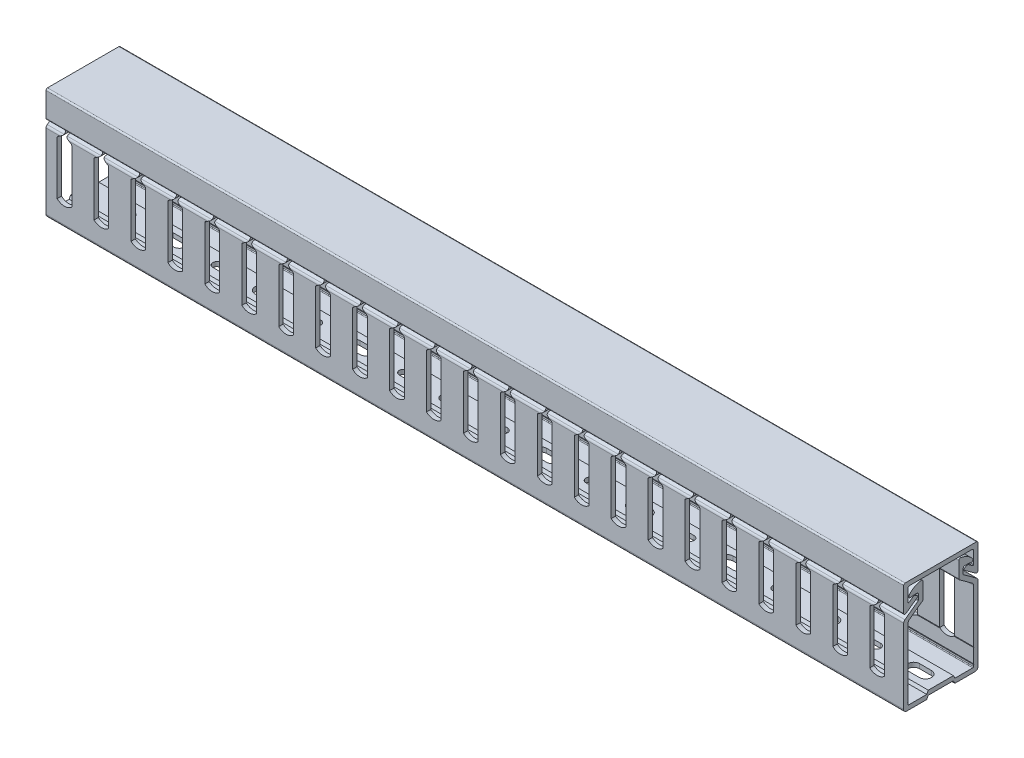
SolidWorks part; units mm, degrees
ref_plane "Alzado" through (0, 0, 0) normal (0, 0, 1) x (1, 0, 0)
ref_plane "Planta" through (0, 0, 0) normal (0, 1, 0) x (1, 0, 0)
ref_plane "Vista lateral" through (0, 0, 0) normal (1, 0, 0) x (0, 0, -1)
sketch "Croquis1" plane through (0, 0, 0) normal (1, 0, 0) x (0, 0, -1)
  line L0 (19.2861, 41.3685) -> (12.1583, 46.5609)
  line L1 (16.9056, 40.2266) -> (9.9464, 45.2924)
  line L2 (17.1611, 50.9204) -> (17.1611, 50.9657)
  line L3 (-7.5409, 0.7912) -> (-6.7469, 2.38)
  line L4 (-6.7469, 2.38) -> (-3.175, 2.38)
  line L5 (-7.5413, -1.5888) -> (-6.7469, 0)
  line L6 (-6.7469, 0) -> (-3.175, 0)
  line L7 (-7.5413, -1.5888) -> (-18.3513, -1.5888)
  line L8 (-3.175, 2.38) -> (3.175, 2.38)
  line L9 (-3.175, 0) -> (3.175, 0)
  line L10 (-17.5588, 10.0456) -> (-17.5588, 2.4512)
  line L11 (-17.162, 0.7912) -> (-7.5409, 0.7912)
  line L12 (-17.856, 2.2796) -> (-17.5588, 2.4512)
  line L13 (-17.856, 2.2796) -> (-17.5588, 2.1081)
  line L14 (-17.5588, 2.1081) -> (-17.5588, 1.1881)
  line L15 (-17.856, 10.2171) -> (-17.5588, 10.0456)
  line L16 (-17.856, 10.2171) -> (-17.5588, 10.3887)
  line L17 (17.5588, 10.0456) -> (17.5588, 2.4512)
  line L18 (17.5588, 2.1081) -> (17.5588, 1.1881)
  line L19 (17.856, 2.2796) -> (17.5588, 2.1081)
  line L20 (17.856, 2.2796) -> (17.5588, 2.4512)
  line L21 (17.856, 10.2171) -> (17.5588, 10.3887)
  line L22 (17.856, 10.2171) -> (17.5588, 10.0456)
  line L23 (17.5588, 38.9431) -> (17.5588, 10.3887)
  line L24 (19.9388, -0.0013) -> (19.9388, 40.0854)
  line L25 (12.0017, 46.8688) -> (12.0017, 49.624)
  line L26 (9.6198, 45.9342) -> (9.6198, 54.439)
  line L27 (14.842, 50.4074) -> (16.2738, 50.1687)
  line L28 (12.7954, 50.4177) -> (14.7167, 50.4177)
  line L29 (-19.2861, 41.3685) -> (-12.1583, 46.5609)
  line L30 (-16.9056, 40.2266) -> (-9.9464, 45.2924)
  line L31 (-9.6198, 45.9342) -> (-9.6198, 54.439)
  line L32 (-12.7954, 50.4177) -> (-14.7167, 50.4177)
  line L33 (-12.0017, 46.8688) -> (-12.0017, 49.624)
  line L34 (-14.842, 50.4074) -> (-16.2738, 50.1687)
  line L35 (-17.1611, 50.9204) -> (-17.1611, 50.9657)
  line L36 (-17.5588, 38.9431) -> (-17.5588, 10.3887)
  line L37 (-19.9388, -0.0013) -> (-19.9388, 40.0854)
  line L38 (3.175, 0) -> (6.7469, 0)
  line L39 (6.7469, 0) -> (7.5413, -1.5888)
  line L40 (7.5413, -1.5888) -> (18.3513, -1.5888)
  line L41 (17.162, 0.7912) -> (7.5413, 0.7912)
  line L42 (7.5413, 0.7912) -> (6.7469, 2.38)
  line L43 (6.7469, 2.38) -> (3.175, 2.38)
  arc A0 (-17.5588, 1.1881) -> (-17.162, 0.7912) centre (-17.162, 1.1881) ccw
  arc A1 (-19.9388, -0.0013) -> (-18.3513, -1.5888) centre (-18.3513, -0.0013) ccw
  arc A2 (17.162, 0.7912) -> (17.5588, 1.1881) centre (17.162, 1.1881) ccw
  arc A3 (18.3513, -1.5888) -> (19.9388, -0.0013) centre (18.3513, -0.0013) ccw
  arc A4 (19.9388, 40.0854) -> (19.2861, 41.3685) centre (18.3513, 40.0854) ccw
  arc A5 (17.5588, 38.9431) -> (16.9056, 40.2266) centre (15.9713, 38.9431) ccw
  arc A6 (12.0017, 46.8688) -> (12.1583, 46.5609) centre (12.3827, 46.8688) ccw
  arc A7 (9.6198, 45.9342) -> (9.9464, 45.2924) centre (10.4136, 45.9342) ccw
  arc A8 (12.7954, 50.4177) -> (12.0017, 49.624) centre (12.7954, 49.624) ccw
  arc A9 (10.688, 55.1838) -> (9.6198, 54.439) centre (10.4136, 54.439) ccw
  arc A10 (16.86, 51.7867) -> (10.688, 55.1838) centre (9.3251, 45.4023) ccw
  arc A11 (17.1611, 50.9657) -> (16.86, 51.7867) centre (15.8911, 50.9657) ccw
  arc A12 (16.2738, 50.1687) -> (17.1611, 50.9204) centre (16.3991, 50.9204) ccw
  arc A13 (14.842, 50.4074) -> (14.7167, 50.4177) centre (14.7167, 49.6557) ccw
  arc A14 (-9.9464, 45.2924) -> (-9.6198, 45.9342) centre (-10.4136, 45.9342) ccw
  arc A15 (-16.9056, 40.2266) -> (-17.5588, 38.9431) centre (-15.9713, 38.9431) ccw
  arc A16 (-19.2861, 41.3685) -> (-19.9388, 40.0854) centre (-18.3513, 40.0854) ccw
  arc A17 (-9.6198, 54.439) -> (-10.688, 55.1838) centre (-10.4136, 54.439) ccw
  arc A18 (-16.86, 51.7867) -> (-17.1611, 50.9657) centre (-15.8911, 50.9657) ccw
  arc A19 (-12.1583, 46.5609) -> (-12.0017, 46.8688) centre (-12.3827, 46.8688) ccw
  arc A20 (-12.0017, 49.624) -> (-12.7954, 50.4177) centre (-12.7954, 49.624) ccw
  arc A21 (-14.7167, 50.4177) -> (-14.842, 50.4074) centre (-14.7167, 49.6557) ccw
  arc A22 (-17.1611, 50.9204) -> (-16.2738, 50.1687) centre (-16.3991, 50.9204) ccw
  arc A23 (-10.688, 55.1838) -> (-16.86, 51.7867) centre (-9.3251, 45.4023) ccw
  point P92 (0, 0)
extrude "Saliente-Extruir1" add sketch "Croquis1" along normal mid plane 762
sketch "Croquis5" plane through (0, 2.38, 0) normal (0, 1, 0) x (1, 0, 0)
  line L157 (-379.0156, -3.2514) -> (-381, -3.2514)
  line L158 (-379.0156, 3.251) -> (-381, 3.251)
  line L159 (-335.6864, 3.251) -> (-329.3364, 3.251)
  line L160 (-335.6864, -3.2514) -> (-329.3364, -3.2514)
  line L161 (-235.6612, -3.2514) -> (-229.3112, -3.2514)
  line L162 (-235.6612, 3.251) -> (-229.3112, 3.251)
  line L163 (-285.6738, -3.2514) -> (-279.3238, -3.2514)
  line L164 (-285.6738, 3.251) -> (-279.3238, 3.251)
  line L165 (-185.6486, -3.2514) -> (-179.2986, -3.2514)
  line L166 (-185.6486, 3.251) -> (-182.1992, 3.251)
  line L167 (-309.2402, 2.2477) -> (-305.7446, 2.2477)
  line L168 (-309.2402, -2.2481) -> (-305.7446, -2.2481)
  line L169 (-355.7826, -2.2481) -> (-359.2782, -2.2481)
  line L170 (-355.7826, 2.2477) -> (-359.2782, 2.2477)
  line L171 (-259.2276, -2.2481) -> (-255.732, -2.2481)
  line L172 (-259.2276, 2.2477) -> (-255.732, 2.2477)
  line L173 (-209.215, -2.2481) -> (-205.7194, -2.2481)
  line L174 (-209.215, 2.2477) -> (-205.7194, 2.2477)
  line L188 (-398.7832, -0.0002) -> (-161.8215, -0.0002) construction
  arc A105 (-379.0156, -3.2514) -> (-379.0156, 3.251) centre (-379.0156, -0.0002) ccw
  arc A106 (-329.3364, -3.2514) -> (-329.3364, 3.251) centre (-329.3364, -0.0002) ccw
  arc A107 (-335.6864, 3.251) -> (-335.6864, -3.2514) centre (-335.6864, -0.0002) ccw
  circle A108 centre (-332.5114, -0.0002) radius 6.677
  circle A109 centre (-332.5114, -0.0002) radius 7.4708
  circle A110 centre (-232.4862, -0.0002) radius 6.677
  circle A111 centre (-232.4862, -0.0002) radius 7.4708
  arc A112 (-229.3112, -3.2514) -> (-229.3112, 3.251) centre (-229.3112, -0.0002) ccw
  arc A113 (-235.6612, 3.251) -> (-235.6612, -3.2514) centre (-235.6612, -0.0002) ccw
  arc A114 (-279.3238, -3.2514) -> (-279.3238, 3.251) centre (-279.3238, -0.0002) ccw
  arc A115 (-285.6738, 3.251) -> (-285.6738, -3.2514) centre (-285.6738, -0.0002) ccw
  arc A116 (-179.2986, -3.2514) -> (-178.0729, -3.0115) centre (-179.2986, -0.0002) ccw
  arc A117 (-185.6486, 3.251) -> (-185.6486, -3.2514) centre (-185.6486, -0.0002) ccw
  arc A118 (-309.2402, 2.2477) -> (-309.2402, -2.2481) centre (-309.2402, -0.0002) ccw
  arc A119 (-305.7446, -2.2481) -> (-305.7446, 2.2477) centre (-305.7446, -0.0002) ccw
  arc A120 (-359.2782, 2.2477) -> (-359.2782, -2.2481) centre (-359.2782, -0.0002) ccw
  arc A121 (-355.7826, -2.2481) -> (-355.7826, 2.2477) centre (-355.7826, -0.0002) ccw
  arc A122 (-255.732, -2.2481) -> (-255.732, 2.2477) centre (-255.732, -0.0002) ccw
  arc A123 (-259.2276, 2.2477) -> (-259.2276, -2.2481) centre (-259.2276, -0.0002) ccw
  arc A124 (-205.7194, -2.2481) -> (-205.7194, 2.2477) centre (-205.7194, -0.0002) ccw
  arc A125 (-209.215, 2.2477) -> (-209.215, -2.2481) centre (-209.215, -0.0002) ccw
  point P817 (-381, 3.251)
  point P818 (-381, -3.2514)
  point P820 (-359.2782, 2.2477)
  point P821 (-359.2782, -2.2481)
  point P823 (-361.5261, -0.0002)
  point P824 (-353.5347, -0.0002)
  point P826 (-285.6738, 3.251)
  point P827 (-285.6738, -3.2514)
  point P829 (-288.925, -0.0002)
  point P830 (-276.0726, -0.0002)
sketch "Croquis6" plane through (0, 2.38, 0) normal (0, 1, 0) x (1, 0, 0)
  line L5 (0, 0) -> (-149.8099, 0) construction
  line L6 (-382.9844, 0) -> (-379.0156, 0) construction
  line L7 (-382.9844, 3.25) -> (-379.0156, 3.25)
  line L8 (-382.9844, -3.25) -> (-379.0156, -3.25)
  line L10 (-381, 6.7469) -> (-381, -6.7469) construction
  line L11 (-355.7826, 0) -> (-359.2782, 0) construction
  line L12 (-355.7826, -2.25) -> (-359.2782, -2.25)
  line L13 (-355.7826, 2.25) -> (-359.2782, 2.25)
  line L14 (-305.7446, 0) -> (-309.2402, 0) construction
  line L15 (-305.7446, -2.25) -> (-309.2402, -2.25)
  line L16 (-305.7446, 2.25) -> (-309.2402, 2.25)
  line L17 (-255.7066, 0) -> (-259.2022, 0) construction
  line L18 (-255.7066, -2.25) -> (-259.2022, -2.25)
  line L19 (-255.7066, 2.25) -> (-259.2022, 2.25)
  line L20 (-205.6686, 0) -> (-209.1642, 0) construction
  line L21 (-205.6686, -2.25) -> (-209.1642, -2.25)
  line L22 (-205.6686, 2.25) -> (-209.1642, 2.25)
  line L23 (-155.6306, 0) -> (-159.1262, 0) construction
  line L24 (-155.6306, -2.25) -> (-159.1262, -2.25)
  line L25 (-155.6306, 2.25) -> (-159.1262, 2.25)
  line L26 (-105.5926, 0) -> (-109.0882, 0) construction
  line L27 (-105.5926, -2.25) -> (-109.0882, -2.25)
  line L28 (-105.5926, 2.25) -> (-109.0882, 2.25)
  line L29 (-55.5546, 0) -> (-59.0502, 0) construction
  line L30 (-55.5546, -2.25) -> (-59.0502, -2.25)
  line L31 (-55.5546, 2.25) -> (-59.0502, 2.25)
  line L32 (-5.5166, 0) -> (-9.0122, 0) construction
  line L33 (-5.5166, -2.25) -> (-9.0122, -2.25)
  line L34 (-5.5166, 2.25) -> (-9.0122, 2.25)
  line L35 (44.5214, 0) -> (41.0258, 0) construction
  line L36 (44.5214, -2.25) -> (41.0258, -2.25)
  line L37 (44.5214, 2.25) -> (41.0258, 2.25)
  line L38 (94.5594, 0) -> (91.0638, 0) construction
  line L39 (94.5594, -2.25) -> (91.0638, -2.25)
  line L40 (94.5594, 2.25) -> (91.0638, 2.25)
  line L41 (144.5974, 0) -> (141.1018, 0) construction
  line L42 (144.5974, -2.25) -> (141.1018, -2.25)
  line L43 (144.5974, 2.25) -> (141.1018, 2.25)
  line L44 (194.6354, 0) -> (191.1398, 0) construction
  line L45 (194.6354, -2.25) -> (191.1398, -2.25)
  line L46 (194.6354, 2.25) -> (191.1398, 2.25)
  line L47 (244.6734, 0) -> (241.1778, 0) construction
  line L48 (244.6734, -2.25) -> (241.1778, -2.25)
  line L49 (244.6734, 2.25) -> (241.1778, 2.25)
  line L50 (294.7114, 0) -> (291.2158, 0) construction
  line L51 (294.7114, -2.25) -> (291.2158, -2.25)
  line L52 (294.7114, 2.25) -> (291.2158, 2.25)
  line L53 (344.7494, 0) -> (341.2538, 0) construction
  line L54 (344.7494, -2.25) -> (341.2538, -2.25)
  line L55 (344.7494, 2.25) -> (341.2538, 2.25)
  line L56 (394.7874, 0) -> (391.2918, 0) construction
  line L57 (394.7874, -2.25) -> (391.2918, -2.25)
  line L58 (394.7874, 2.25) -> (391.2918, 2.25)
  arc A3 (-382.9844, 3.25) -> (-382.9844, -3.25) centre (-382.9844, 0) ccw
  arc A4 (-379.0156, -3.25) -> (-379.0156, 3.25) centre (-379.0156, 0) ccw
  arc A5 (-355.7826, -2.25) -> (-355.7826, 2.25) centre (-355.7826, 0) ccw
  arc A6 (-359.2782, 2.25) -> (-359.2782, -2.25) centre (-359.2782, 0) ccw
  arc A7 (-305.7446, -2.25) -> (-305.7446, 2.25) centre (-305.7446, 0) ccw
  arc A8 (-309.2402, 2.25) -> (-309.2402, -2.25) centre (-309.2402, 0) ccw
  arc A9 (-255.7066, -2.25) -> (-255.7066, 2.25) centre (-255.7066, 0) ccw
  arc A10 (-259.2022, 2.25) -> (-259.2022, -2.25) centre (-259.2022, 0) ccw
  arc A11 (-205.6686, -2.25) -> (-205.6686, 2.25) centre (-205.6686, 0) ccw
  arc A12 (-209.1642, 2.25) -> (-209.1642, -2.25) centre (-209.1642, 0) ccw
  arc A13 (-155.6306, -2.25) -> (-155.6306, 2.25) centre (-155.6306, 0) ccw
  arc A14 (-159.1262, 2.25) -> (-159.1262, -2.25) centre (-159.1262, 0) ccw
  arc A15 (-105.5926, -2.25) -> (-105.5926, 2.25) centre (-105.5926, 0) ccw
  arc A16 (-109.0882, 2.25) -> (-109.0882, -2.25) centre (-109.0882, 0) ccw
  arc A17 (-55.5546, -2.25) -> (-55.5546, 2.25) centre (-55.5546, 0) ccw
  arc A18 (-59.0502, 2.25) -> (-59.0502, -2.25) centre (-59.0502, 0) ccw
  arc A19 (-5.5166, -2.25) -> (-5.5166, 2.25) centre (-5.5166, 0) ccw
  arc A20 (-9.0122, 2.25) -> (-9.0122, -2.25) centre (-9.0122, 0) ccw
  arc A21 (44.5214, -2.25) -> (44.5214, 2.25) centre (44.5214, 0) ccw
  arc A22 (41.0258, 2.25) -> (41.0258, -2.25) centre (41.0258, 0) ccw
  arc A23 (94.5594, -2.25) -> (94.5594, 2.25) centre (94.5594, 0) ccw
  arc A24 (91.0638, 2.25) -> (91.0638, -2.25) centre (91.0638, 0) ccw
  arc A25 (144.5974, -2.25) -> (144.5974, 2.25) centre (144.5974, 0) ccw
  arc A26 (141.1018, 2.25) -> (141.1018, -2.25) centre (141.1018, 0) ccw
  arc A27 (194.6354, -2.25) -> (194.6354, 2.25) centre (194.6354, 0) ccw
  arc A28 (191.1398, 2.25) -> (191.1398, -2.25) centre (191.1398, 0) ccw
  arc A29 (244.6734, -2.25) -> (244.6734, 2.25) centre (244.6734, 0) ccw
  arc A30 (241.1778, 2.25) -> (241.1778, -2.25) centre (241.1778, 0) ccw
  arc A31 (294.7114, -2.25) -> (294.7114, 2.25) centre (294.7114, 0) ccw
  arc A32 (291.2158, 2.25) -> (291.2158, -2.25) centre (291.2158, 0) ccw
  arc A33 (344.7494, -2.25) -> (344.7494, 2.25) centre (344.7494, 0) ccw
  arc A34 (341.2538, 2.25) -> (341.2538, -2.25) centre (341.2538, 0) ccw
  arc A35 (394.7874, -2.25) -> (394.7874, 2.25) centre (394.7874, 0) ccw
  arc A36 (391.2918, 2.25) -> (391.2918, -2.25) centre (391.2918, 0) ccw
  point P0 (-381, 0)
  point P8 (-357.5304, 0)
  point P26 (-307.4924, 0)
  point P33 (-257.4544, 0)
  point P40 (-207.4164, 0)
  point P47 (-157.3784, 0)
  point P54 (-107.3404, 0)
  point P61 (-57.3024, 0)
  point P68 (-7.2644, 0)
  point P75 (42.7736, 0)
  point P82 (92.8116, 0)
  point P89 (142.8496, 0)
  point P96 (192.8876, 0)
  point P103 (242.9256, 0)
  point P110 (292.9636, 0)
  point P117 (343.0016, 0)
  point P124 (393.0396, 0)
  dimension "D1" = 6.5
  dimension "D3" = 4.5
  dimension "D2" = 3.9687
  dimension "D4" = 3.4957
  dimension "D5" = 19.7374
  dimension "D7" = 50.038
  dimension "D6" = 16
extrude "Cortar-Extruir3" cut sketch "Croquis6" against normal through all
sketch "Croquis7" plane through (0, 2.38, 0) normal (0, 1, 0) x (1, 0, 0)
  line L0 (431.9082, 0) -> (-431.9082, 0) construction
  line L1 (-335.6864, 0) -> (-329.3364, 0) construction
  line L2 (-335.6864, 3.2512) -> (-329.3364, 3.2512)
  line L3 (-335.6864, -3.2512) -> (-329.3364, -3.2512)
  line L4 (-381, 17.162) -> (-381, 7.5413) construction
  line L5 (-285.6738, 0) -> (-279.3238, 0) construction
  line L6 (-285.6738, 3.2512) -> (-279.3238, 3.2512)
  line L7 (-285.6738, -3.2512) -> (-279.3238, -3.2512)
  line L8 (-235.6612, 0) -> (-229.3112, 0) construction
  line L9 (-235.6612, 3.2512) -> (-229.3112, 3.2512)
  line L10 (-235.6612, -3.2512) -> (-229.3112, -3.2512)
  line L11 (-185.6486, 0) -> (-179.2986, 0) construction
  line L12 (-185.6486, 3.2512) -> (-179.2986, 3.2512)
  line L13 (-185.6486, -3.2512) -> (-179.2986, -3.2512)
  line L14 (-135.636, 0) -> (-129.286, 0) construction
  line L15 (-135.636, 3.2512) -> (-129.286, 3.2512)
  line L16 (-135.636, -3.2512) -> (-129.286, -3.2512)
  line L17 (-85.6234, 0) -> (-79.2734, 0) construction
  line L18 (-85.6234, 3.2512) -> (-79.2734, 3.2512)
  line L19 (-85.6234, -3.2512) -> (-79.2734, -3.2512)
  line L20 (-35.6108, 0) -> (-29.2608, 0) construction
  line L21 (-35.6108, 3.2512) -> (-29.2608, 3.2512)
  line L22 (-35.6108, -3.2512) -> (-29.2608, -3.2512)
  line L23 (14.4018, 0) -> (20.7518, 0) construction
  line L24 (14.4018, 3.2512) -> (20.7518, 3.2512)
  line L25 (14.4018, -3.2512) -> (20.7518, -3.2512)
  line L26 (64.4144, 0) -> (70.7644, 0) construction
  line L27 (64.4144, 3.2512) -> (70.7644, 3.2512)
  line L28 (64.4144, -3.2512) -> (70.7644, -3.2512)
  line L29 (114.427, 0) -> (120.777, 0) construction
  line L30 (114.427, 3.2512) -> (120.777, 3.2512)
  line L31 (114.427, -3.2512) -> (120.777, -3.2512)
  line L32 (164.4396, 0) -> (170.7896, 0) construction
  line L33 (164.4396, 3.2512) -> (170.7896, 3.2512)
  line L34 (164.4396, -3.2512) -> (170.7896, -3.2512)
  line L35 (214.4522, 0) -> (220.8022, 0) construction
  line L36 (214.4522, 3.2512) -> (220.8022, 3.2512)
  line L37 (214.4522, -3.2512) -> (220.8022, -3.2512)
  line L38 (264.4648, 0) -> (270.8148, 0) construction
  line L39 (264.4648, 3.2512) -> (270.8148, 3.2512)
  line L40 (264.4648, -3.2512) -> (270.8148, -3.2512)
  line L41 (314.4774, 0) -> (320.8274, 0) construction
  line L42 (314.4774, 3.2512) -> (320.8274, 3.2512)
  line L43 (314.4774, -3.2512) -> (320.8274, -3.2512)
  line L44 (364.49, 0) -> (370.84, 0) construction
  line L45 (364.49, 3.2512) -> (370.84, 3.2512)
  line L46 (364.49, -3.2512) -> (370.84, -3.2512)
  arc A0 (-335.6864, 3.2512) -> (-335.6864, -3.2512) centre (-335.6864, 0) ccw
  arc A1 (-329.3364, -3.2512) -> (-329.3364, 3.2512) centre (-329.3364, 0) ccw
  arc A2 (-285.6738, 3.2512) -> (-285.6738, -3.2512) centre (-285.6738, 0) ccw
  arc A3 (-279.3238, -3.2512) -> (-279.3238, 3.2512) centre (-279.3238, 0) ccw
  arc A4 (-235.6612, 3.2512) -> (-235.6612, -3.2512) centre (-235.6612, 0) ccw
  arc A5 (-229.3112, -3.2512) -> (-229.3112, 3.2512) centre (-229.3112, 0) ccw
  arc A6 (-185.6486, 3.2512) -> (-185.6486, -3.2512) centre (-185.6486, 0) ccw
  arc A7 (-179.2986, -3.2512) -> (-179.2986, 3.2512) centre (-179.2986, 0) ccw
  arc A8 (-135.636, 3.2512) -> (-135.636, -3.2512) centre (-135.636, 0) ccw
  arc A9 (-129.286, -3.2512) -> (-129.286, 3.2512) centre (-129.286, 0) ccw
  arc A10 (-85.6234, 3.2512) -> (-85.6234, -3.2512) centre (-85.6234, 0) ccw
  arc A11 (-79.2734, -3.2512) -> (-79.2734, 3.2512) centre (-79.2734, 0) ccw
  arc A12 (-35.6108, 3.2512) -> (-35.6108, -3.2512) centre (-35.6108, 0) ccw
  arc A13 (-29.2608, -3.2512) -> (-29.2608, 3.2512) centre (-29.2608, 0) ccw
  arc A14 (14.4018, 3.2512) -> (14.4018, -3.2512) centre (14.4018, 0) ccw
  arc A15 (20.7518, -3.2512) -> (20.7518, 3.2512) centre (20.7518, 0) ccw
  arc A16 (64.4144, 3.2512) -> (64.4144, -3.2512) centre (64.4144, 0) ccw
  arc A17 (70.7644, -3.2512) -> (70.7644, 3.2512) centre (70.7644, 0) ccw
  arc A18 (114.427, 3.2512) -> (114.427, -3.2512) centre (114.427, 0) ccw
  arc A19 (120.777, -3.2512) -> (120.777, 3.2512) centre (120.777, 0) ccw
  arc A20 (164.4396, 3.2512) -> (164.4396, -3.2512) centre (164.4396, 0) ccw
  arc A21 (170.7896, -3.2512) -> (170.7896, 3.2512) centre (170.7896, 0) ccw
  arc A22 (214.4522, 3.2512) -> (214.4522, -3.2512) centre (214.4522, 0) ccw
  arc A23 (220.8022, -3.2512) -> (220.8022, 3.2512) centre (220.8022, 0) ccw
  arc A24 (264.4648, 3.2512) -> (264.4648, -3.2512) centre (264.4648, 0) ccw
  arc A25 (270.8148, -3.2512) -> (270.8148, 3.2512) centre (270.8148, 0) ccw
  arc A26 (314.4774, 3.2512) -> (314.4774, -3.2512) centre (314.4774, 0) ccw
  arc A27 (320.8274, -3.2512) -> (320.8274, 3.2512) centre (320.8274, 0) ccw
  arc A28 (364.49, 3.2512) -> (364.49, -3.2512) centre (364.49, 0) ccw
  arc A29 (370.84, -3.2512) -> (370.84, 3.2512) centre (370.84, 0) ccw
  point P4 (0, 0)
  point P9 (-332.5114, 0)
  point P16 (-282.4988, 0)
  point P28 (-232.4862, 0)
  point P35 (-182.4736, 0)
  point P42 (-132.461, 0)
  point P49 (-82.4484, 0)
  point P56 (-32.4358, 0)
  point P63 (17.5768, 0)
  point P70 (67.5894, 0)
  point P77 (117.602, 0)
  point P84 (167.6146, 0)
  point P91 (217.6272, 0)
  point P98 (267.6398, 0)
  point P105 (317.6524, 0)
  point P112 (367.665, 0)
  dimension "D5" = 50.0126
  dimension "D1" = 6.5024
  dimension "D2" = 6.35
  dimension "D3" = 45.3136
  dimension "D4" = 15
extrude "Cortar-Extruir4" cut sketch "Croquis7" against normal through all
sketch "Croquis4" plane through (0, 0, 19.9388) normal (0, 0, 1) x (1, 0, 0)
  line L0 (-375.031, 23.9974) -> (-367.157, 23.9974) construction
  line L1 (-371.094, 23.9974) -> (-371.094, 31.3497) construction
  line L2 (-367.157, 23.9974) -> (-355.219, 23.9974) construction
  line L3 (-356.0128, 55.2327) -> (-366.3633, 55.2327)
  line L4 (-369.9565, 42.2005) -> (-367.4745, 43.7644)
  line L5 (-369.9565, 40.9305) -> (-367.4745, 39.3666)
  line L6 (-367.157, 54.439) -> (-367.157, 44.3994)
  line L7 (-367.157, 38.7316) -> (-367.157, 23.9974)
  line L8 (-361.188, 23.9974) -> (-361.188, 33.0481) construction
  line L9 (-355.219, 38.7316) -> (-355.219, 23.9974)
  line L10 (-352.4195, 40.9305) -> (-354.9015, 39.3666)
  line L11 (-352.4195, 42.2005) -> (-354.9015, 43.7644)
  line L12 (-355.219, 54.439) -> (-355.219, 44.3994)
  line L13 (-375.031, 23.9974) -> (-375.031, 10.2476)
  line L14 (-375.031, 10.2476) -> (-367.157, 10.2476) construction
  line L15 (381, -1.5888) -> (-381, -1.5888) construction
  line L17 (-367.157, 10.2476) -> (-367.157, 23.9974)
  line L47 (-366.3633, 55.2327) -> (-375.8248, 55.2327)
  line L99 (-375.031, 38.7316) -> (-375.031, 23.9974)
  line L100 (-375.031, 54.439) -> (-375.031, 44.3994)
  line L103 (-372.2315, 40.9305) -> (-374.7135, 39.3666)
  line L104 (-372.2315, 42.2005) -> (-374.7135, 43.7644)
  line L106 (-381, 55.2327) -> (-375.8248, 55.2327)
  line L107 (-381, 55.2327) -> (-381, -1.5888)
  arc A0 (-367.157, 54.439) -> (-366.3633, 55.2327) centre (-366.3633, 54.439) cw
  arc A1 (-367.157, 44.3994) -> (-367.4745, 43.7644) centre (-367.9508, 44.3994) cw
  arc A2 (-367.4745, 39.3666) -> (-367.157, 38.7316) centre (-367.9508, 38.7316) cw
  arc A3 (-369.9565, 40.9305) -> (-369.9565, 42.2005) centre (-369.4803, 41.5655) cw
  arc A4 (-354.9015, 39.3666) -> (-355.219, 38.7316) centre (-354.4253, 38.7316) ccw
  arc A5 (-352.4195, 40.9305) -> (-352.4195, 42.2005) centre (-352.8957, 41.5655) ccw
  arc A6 (-355.219, 44.3994) -> (-354.9015, 43.7644) centre (-354.4253, 44.3994) ccw
  arc A7 (-355.219, 54.439) -> (-356.0128, 55.2327) centre (-356.0128, 54.439) ccw
  arc A37 (-375.031, 10.2476) -> (-367.157, 10.2476) centre (-371.094, 14.464) ccw
  arc A79 (-372.2315, 40.9305) -> (-372.2315, 42.2005) centre (-372.7077, 41.5655) ccw
  arc A80 (-374.7135, 39.3666) -> (-375.031, 38.7316) centre (-374.2372, 38.7316) ccw
  arc A81 (-375.031, 44.3994) -> (-374.7135, 43.7644) centre (-374.2372, 44.3994) ccw
  arc A82 (-375.031, 54.439) -> (-375.8248, 55.2327) centre (-375.8248, 54.439) ccw
  point P0 (-381, 55.2327)
  point P18 (-381, 55.2327)
  point P33 (-361.188, 55.2327)
  line M606 (381, 40.0854) -> (-381, 40.0854)
  dimension "D1" = 11.8364
  dimension "D2" = 56.8215
extrude "Cortar-Extruir2" cut sketch "Croquis4" against normal blind 762 contours L103 A80 L99 L13 A37 L17 L7 A2 L5 M606 | A82 L100 A81 L104 A79 L103 L5 A3 L4 A1 L6 A0 L47 M606
pattern_linear "MatrizL1" count 39 spacing 19.812 along (1, 0, 0) of "Cortar-Extruir2"
sketch "Croquis2" plane through (381, 0, 0) normal (1, 0, 0) x (0, 0, -1)
  line L0 (-19.1454, 58.3552) -> (19.1454, 58.3552)
  line L1 (-16.7656, 55.9752) -> (16.7656, 55.9752)
  line L2 (19.9392, 44.6261) -> (19.9392, 57.5615)
  line L3 (18.6821, 43.9816) -> (12.5201, 48.4108)
  line L4 (17.5594, 55.1813) -> (17.5577, 48.4602)
  line L5 (17.1554, 48.254) -> (15.1574, 49.6901)
  line L6 (-19.9392, 44.6261) -> (-19.9392, 57.5615)
  line L7 (-18.6821, 43.9816) -> (-12.5201, 48.4108)
  line L8 (-17.5594, 55.1813) -> (-17.5577, 48.4602)
  line L9 (-17.1554, 48.254) -> (-15.1574, 49.6901)
  line L10 (0, 0) -> (0, 58.3552) construction
  line L11 (7.5413, -1.5888) -> (18.3513, -1.5888) construction
  arc A0 (17.1554, 48.254) -> (17.5577, 48.4602) centre (17.3037, 48.4602) ccw
  arc A1 (13.8793, 49.9491) -> (12.4217, 48.9257) centre (14.3995, 47.6586) ccw
  arc A2 (15.1574, 49.6901) -> (13.8793, 49.9491) centre (14.2309, 48.4011) ccw
  arc A3 (12.4217, 48.9257) -> (12.5201, 48.4108) centre (12.7425, 48.7202) ccw
  arc A4 (18.6821, 43.9816) -> (19.9392, 44.6261) centre (19.1454, 44.6261) ccw
  arc A5 (19.9392, 57.5615) -> (19.1454, 58.3552) centre (19.1454, 57.5615) ccw
  arc A6 (17.5594, 55.1813) -> (16.7656, 55.9752) centre (16.7656, 55.1815) ccw
  arc A7 (-19.9392, 44.6261) -> (-18.6821, 43.9816) centre (-19.1454, 44.6261) ccw
  arc A8 (-13.8793, 49.9491) -> (-15.1574, 49.6901) centre (-14.2309, 48.4011) ccw
  arc A9 (-12.5201, 48.4108) -> (-12.4217, 48.9257) centre (-12.7425, 48.7202) ccw
  arc A10 (-12.4217, 48.9257) -> (-13.8793, 49.9491) centre (-14.3995, 47.6586) ccw
  arc A11 (-17.5577, 48.4602) -> (-17.1554, 48.254) centre (-17.3037, 48.4602) ccw
  arc A12 (-16.7656, 55.9752) -> (-17.5594, 55.1813) centre (-16.7656, 55.1815) ccw
  arc A13 (-19.1454, 58.3552) -> (-19.9392, 57.5615) centre (-19.1454, 57.5615) ccw
  point P41 (0, 58.3552)
  dimension "D1" = 59.944
extrude "Saliente-Extruir2" add sketch "Croquis2" against normal up to surface (762 mm away) separate body up to face at (-381, 26.5287, -13.9522)
sketch "Croquis8" plane through (0, 58.3552, 0) normal (0, 1, 0) x (1, 0, 0)
  line L0 (-381, -19.9392) -> (381, -19.9392) construction
  line L1 (-381, 19.9392) -> (79, 19.9392)
  line L2 (-381, 19.9392) -> (-381, -19.9392)
  line L3 (-381, -19.9392) -> (79, -19.9392)
  line L4 (79, 19.9392) -> (79, -19.9392)
  dimension "D1" = 460
extrude "Cortar-Extruir5" cut sketch "Croquis8" against normal through all flip side to cut
